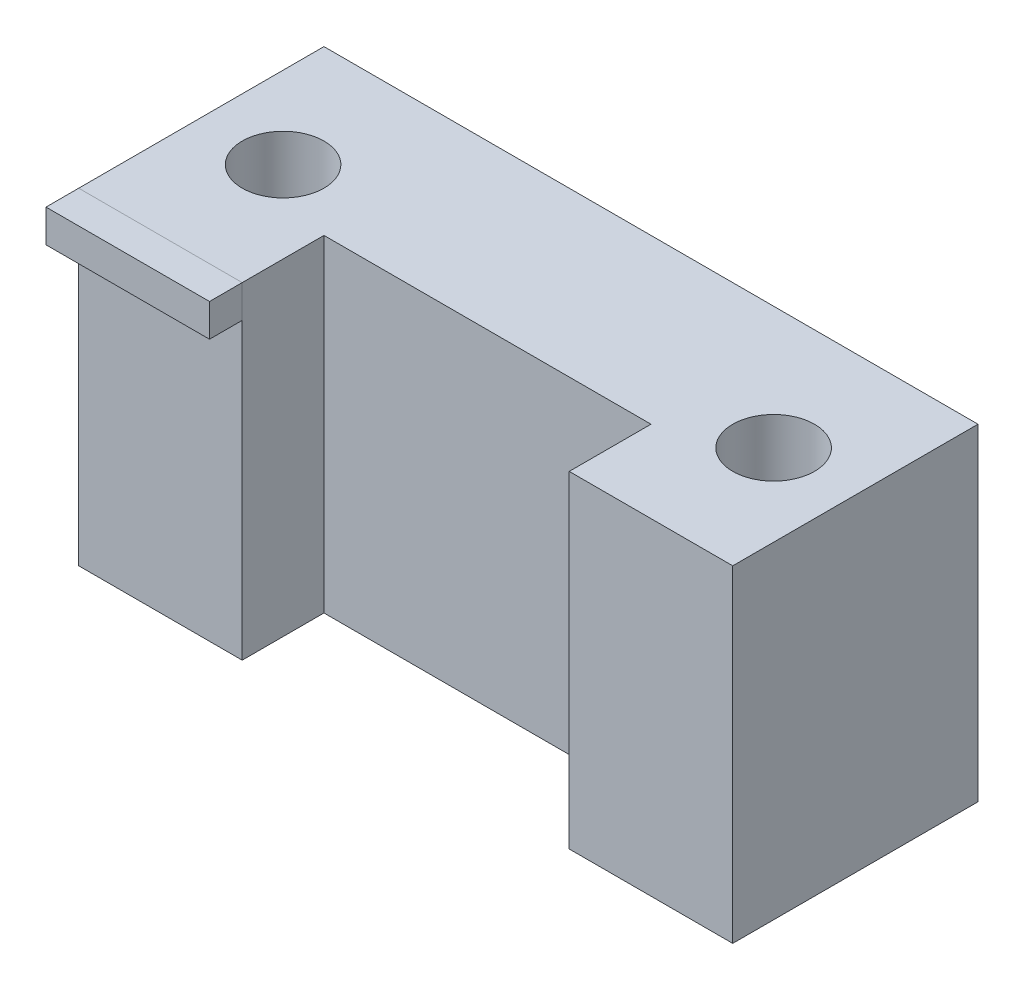
SolidWorks part; units mm, degrees
ref_plane "Front Plane" through (0, 0, 0) normal (0, 0, 1) x (1, 0, 0)
ref_plane "Top Plane" through (0, 0, 0) normal (0, 1, 0) x (1, 0, 0)
ref_plane "Right Plane" through (0, 0, 0) normal (1, 0, 0) x (0, 0, -1)
sketch "Sketch1" plane through (0, 0, 0) normal (0, 1, 0) x (1, 0, 0)
  line L0 (150, 0) -> (200, 0)
  line L1 (0, 0) -> (50, 0)
  line L2 (0, 0) -> (0, 75)
  line L3 (0, 75) -> (200, 75)
  line L4 (200, 0) -> (200, 75)
  line L6 (50, 0) -> (50, 25)
  line L7 (50, 25) -> (150, 25)
  line L8 (150, 0) -> (150, 25)
  line L9 (25, 37.5) -> (175, 37.5) construction
  point P9 (100, 25)
  point P10 (100, 75)
  point P13 (100, 37.5)
  point P14 (200, 37.5)
  dimension "D1" = 25
  dimension "D2" = 200
  dimension "D3" = 100
  dimension "D4" = 75
  dimension "D5" = 150
extrude "Boss-Extrude1" add sketch "Sketch1" along normal blind 100
hole_wizard "Hole1" positions "3DSketch2" profile "Sketch2" legacy end condition through all
sketch3d "3DSketch2"
  point P33 (175, 0, -37.5)
  point P39 (25, 0, -37.5)
  point P42 (0, 0, 0)
  point P43 (25, 0, -37.5)
sketch "Sketch2" plane through (175, 0, -37.5) normal (1, 0, 0) x (0, 0, -1)
  line L0 (0, 0) -> (0, 100)
  line L1 (0, 100) -> (12.5, 100)
  line L2 (12.5, 100) -> (12.5, 0)
  line L3 (12.5, 0) -> (0, 0)
  line L4 (0, 110) -> (0, -10) construction
  dimension "Diameter" = 25
  dimension "Depth" = 100
sketch "Sketch3" plane through (0, 0, 0) normal (0, 0, 1) x (1, 0, 0)
  line L1 (0, 100) -> (50, 100)
  line L2 (0, 100) -> (0, 90)
  line L3 (0, 90) -> (50, 90)
  line L4 (50, 100) -> (50, 90)
  dimension "D1" = 50
  dimension "10" = 10
extrude "Boss-Extrude2" add sketch "Sketch3" along normal blind 10 separate body
